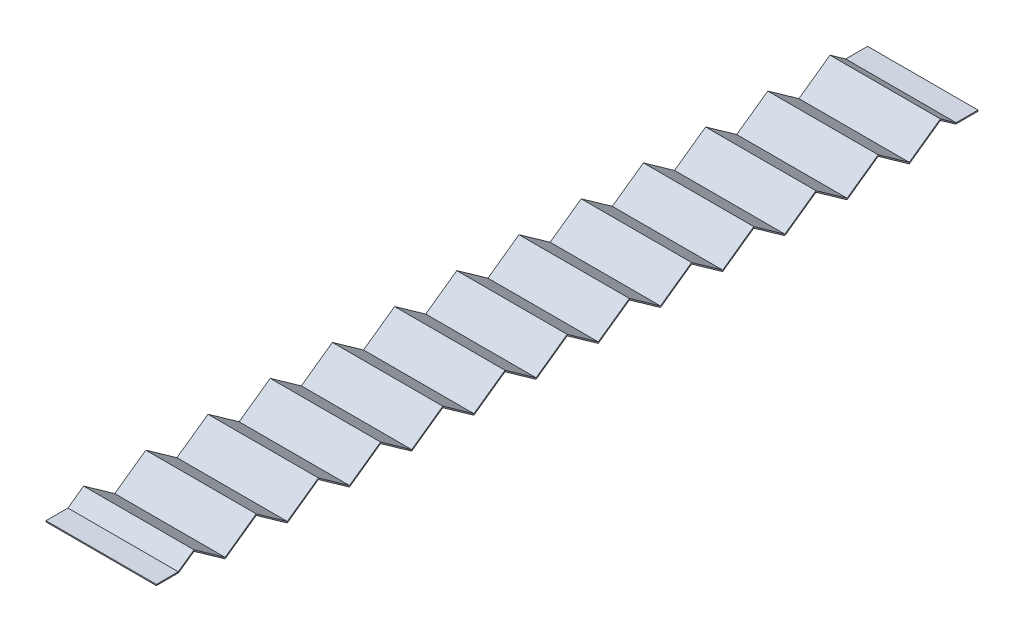
SolidWorks part; units mm, degrees
ref_plane "Front Plane" through (0, 0, 0) normal (0, 0, 1) x (1, 0, 0)
ref_plane "Top Plane" through (0, 0, 0) normal (0, 1, 0) x (1, 0, 0)
ref_plane "Right Plane" through (0, 0, 0) normal (1, 0, 0) x (0, 0, -1)
sketch "Sketch2" plane through (0, 0, 0) normal (0, 0, 1) x (1, 0, 0)
  line L1 (-27.5, 10) -> (27.5, 10)
  line L2 (-27.5, 10) -> (-27.5, 0)
  line L3 (-27.5, 0) -> (27.5, 0)
  line L4 (27.5, 10) -> (27.5, 0)
  point P4 (0, 0)
  dimension "D1" = 10
  dimension "D2" = 55
sketch "Sketch3" plane through (0, 0, 0) normal (1, 0, 0) x (0, 0, -1)
  line L0 (0, 10) -> (372.1539, 10) construction
  line L1 (0, 0) -> (372.1539, 0) construction
  line L3 (10, 5) -> (17.0431, 10)
  line L4 (17.0431, 10) -> (31.1292, 0)
  line L5 (31.1292, 0) -> (45.2154, 10)
  line L6 (45.2154, 10) -> (59.3015, 0)
  line L7 (59.3015, 0) -> (73.3877, 10)
  line L8 (73.3877, 10) -> (87.4738, 0)
  line L9 (87.4738, 0) -> (101.56, 10)
  line L10 (101.56, 10) -> (115.6462, 0)
  line L11 (115.6462, 0) -> (129.7323, 10)
  line L12 (129.7323, 10) -> (143.8185, 0)
  line L13 (143.8185, 0) -> (157.9046, 10)
  line L14 (157.9046, 10) -> (171.9908, 0)
  line L15 (171.9908, 0) -> (186.0769, 10)
  line L16 (186.0769, 10) -> (200.1631, 0)
  line L17 (200.1631, 0) -> (214.2492, 10)
  line L18 (214.2492, 10) -> (228.3354, 0)
  line L19 (0, 10) -> (0, 0) construction
  line L20 (228.3354, 0) -> (242.4215, 10)
  line L21 (242.4215, 10) -> (256.5077, 0)
  line L22 (256.5077, 0) -> (270.5938, 10)
  line L23 (270.5938, 10) -> (284.68, 0)
  line L24 (284.68, 0) -> (298.7662, 10)
  line L25 (298.7662, 10) -> (312.8523, 0)
  line L26 (312.8523, 0) -> (326.9385, 10)
  line L27 (326.9385, 10) -> (341.0246, 0)
  line L28 (341.0246, 0) -> (355.1108, 10)
  line L29 (355.1108, 10) -> (362.1539, 5)
  line L30 (372.1539, 10) -> (372.1539, 0) construction
  line L31 (10, 5) -> (0, 5)
  line L32 (362.1539, 5) -> (372.1539, 5)
  line L33 (372.1539, -12.3958) -> (372.1539, -19.8536) construction
  dimension "D2" = 10
  dimension "D1" = 10
  dimension "D3" = 10
extrude "Extrude-Thin1" add sketch "Sketch3" against normal mid plane 50 thin thin type mid plane wall 0.5
